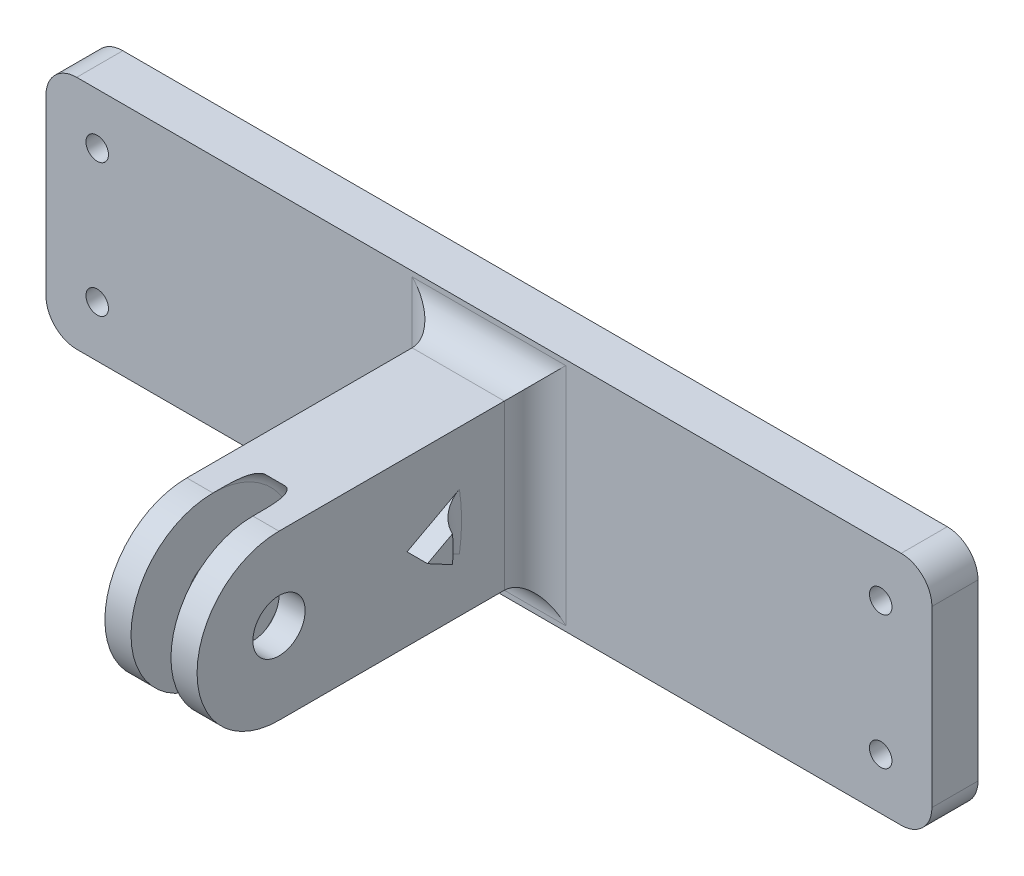
SolidWorks part; units mm, degrees
ref_plane "Front Plane" through (0, 0, 0) normal (0, 0, 1) x (1, 0, 0)
ref_plane "Top Plane" through (0, 0, 0) normal (0, 1, 0) x (1, 0, 0)
ref_plane "Right Plane" through (0, 0, 0) normal (1, 0, 0) x (0, 0, -1)
sketch "Sketch1" plane through (0, 0, 0) normal (0, 0, 1) x (1, 0, 0)
  line L1 (-38.25, 6.5) -> (38.25, 6.5) construction
  line L2 (-38.25, 6.5) -> (-38.25, -6.5) construction
  line L3 (-38.25, -6.5) -> (38.25, -6.5) construction
  line L4 (38.25, 6.5) -> (38.25, -6.5) construction
  line L5 (-38.25, 6.5) -> (38.25, -6.5) construction
  line L6 (-38.25, -6.5) -> (38.25, 6.5) construction
  line L7 (-43.25, 11.5) -> (43.25, 11.5)
  line L8 (-43.25, 11.5) -> (-43.25, -11.5)
  line L9 (-43.25, -11.5) -> (43.25, -11.5)
  line L10 (43.25, 11.5) -> (43.25, -11.5)
  line L11 (-43.25, 11.5) -> (43.25, -11.5) construction
  line L12 (-43.25, -11.5) -> (43.25, 11.5) construction
  circle A0 centre (38.25, 6.5) radius 1.1
  circle A1 centre (38.25, -6.5) radius 1.1
  circle A2 centre (-38.25, -6.5) radius 1.1
  circle A3 centre (-38.25, 6.5) radius 1.1
  point P0 (0, 0)
  point P6 (0, 0)
  dimension "D3" = 2.2
  dimension "D1" = 76.5
  dimension "D2" = 13
  dimension "D4" = 5
  dimension "D5" = 5
extrude "Boss-Extrude1" add sketch "Sketch1" along normal blind 4.5
sketch "Sketch2" plane through (0, 0, 0) normal (0, 0, -1) x (-1, 0, 0)
  line L0 (0, 11.5) -> (0, 0) construction
  line L1 (-43.25, 11.5) -> (43.25, 11.5) construction
  line L2 (0, 0) -> (43.25, 0) construction
  line L3 (43.25, 11.5) -> (43.25, -11.5) construction
  line L4 (-35.6042, 9.5) -> (35.6042, 9.5)
  line L5 (38.25, 2.5) -> (38.25, -2.5)
  line L6 (-38.25, 2.5) -> (-38.25, -2.5)
  line L7 (-35.6042, -9.5) -> (35.6042, -9.5)
  line L8 (5, 9.5) -> (5, -9.5)
  line L9 (-5, 9.5) -> (-5, -9.5)
  arc A0 (35.6042, 9.5) -> (38.25, 2.5) centre (38.25, 6.5) ccw
  arc A1 (-35.6042, 9.5) -> (-38.25, 2.5) centre (-38.25, 6.5) cw
  arc A2 (-35.6042, -9.5) -> (-38.25, -2.5) centre (-38.25, -6.5) ccw
  arc A3 (35.6042, -9.5) -> (38.25, -2.5) centre (38.25, -6.5) cw
  point P18 (38.25, 0)
  point P19 (0, 9.5)
  point P25 (0, -9.5)
  point P26 (-38.25, 0)
  dimension "D1" = 8
  dimension "D2" = 10
  dimension "D3" = 2
extrude "Cut-Extrude1" cut sketch "Sketch2" against normal blind 2 contours A2 L7 L9 L4 A1 L6 | L7 A3 L5 A0 L4 L8 region at (20.4394, 0, 0) region at (-20.4394, 0, 0)
sketch "Sketch3" plane through (0, 0, 0) normal (1, 0, 0) x (0, 0, -1)
  line L0 (0, 0) -> (-29.5, 0) construction
  line L1 (-29.5, 8) -> (-4.5, 8)
  line L2 (-4.5, -11.5) -> (-4.5, 11.5) construction
  line L3 (-4.5, 8) -> (-4.5, -8)
  line L4 (-29.5, -8) -> (-4.5, -8)
  arc A0 (-29.5, 8) -> (-29.5, -8) centre (-29.5, 0) ccw
  circle A1 centre (-29.5, 0) radius 2.55
  point P10 (-4.5, 0)
  dimension "D3" = 5.1
  dimension "D1" = 25
  dimension "D2" = 16
extrude "Boss-Extrude2" add sketch "Sketch3" along normal mid plane 9
sketch "Sketch6" plane through (0, 0, 0) normal (1, 0, 0) x (0, 0, -1)
  circle A0 centre (-29.5, 0) radius 9
  dimension "D1" = 18
extrude "Cut-Extrude3" cut sketch "Sketch6" against normal mid plane 3.9
fillet "Fillet1" radius 3 8 edges at (0, 8, 4.5) (0, -8, 4.5) (4.5, 0, 4.5) (-4.5, 0, 4.5) (43.25, -11.5, 2.25) (-43.25, 11.5, 2.25) (43.25, 11.5, 2.25) (-43.25, -11.5, 2.25)
fillet "Fillet2" radius 1 2 edges at (1.95, 0, 20.5) (-1.95, 0, 20.5)
fillet "Fillet3" radius 1 12 edges at (-38.25, -2.5, 1) (-38.25, 2.5, 1) (-35.6042, 9.5, 1) (-5, -9.5, 1) (-35.6042, -9.5, 1) (35.6042, -9.5, 1) (5, -9.5, 1) (5, 9.5, 1) (35.6042, 9.5, 1) (38.25, 2.5, 1) (38.25, -2.5, 1) (-5, 9.5, 1)
sketch "Sketch7" plane through (4.5, 0, 0) normal (1, 0, 0) x (0, 0, -1)
  line L0 (-29.5, 0) -> (-29.5, -15)
  line L1 (-29.5, 0) -> (-44.5, 0)
  line L2 (-29.5, 0) -> (-29.5, 15)
  line L3 (-29.5, 0) -> (-14.5, 0)
  line L4 (-29.5, 0) -> (-14.5571, -1.3073)
  line L5 (-29.5, 0) -> (-14.5571, 1.3073)
  line L6 (-14.5571, 1.3073) -> (-17, 0)
  line L7 (-17, 0) -> (-14.5571, -1.3073)
  line L8 (-14.5571, 1.3073) -> (-14.5571, -1.3073)
  circle A0 centre (-29.5, 0) radius 15
  point P10 (-29.5, 0)
  dimension "D1" = 30
  dimension "D3" = 5
  dimension "D4" = 5
  dimension "D5" = 12.5
  dimension "D2" = 4
extrude "Boss-Extrude3" add sketch "Sketch7" along normal blind 2 contours L8 L6 L3 | L8 L3 L7 | L3 A0 L8 | L8 A0 L3 region at (4.5, 0.4358, 15.3714) region at (4.5, -0.4358, 15.3714) region at (4.5, -0.4904, 14.5342) region at (4.5, 0.4904, 14.5342)
mirror "Mirror1" about plane through (0, 0, 0) normal (1, 0, 0) of "Boss-Extrude3"
fillet "Fillet4" radius 3 2 edges at (4.5, 0, 14.5) (-4.5, 0, 14.5)
